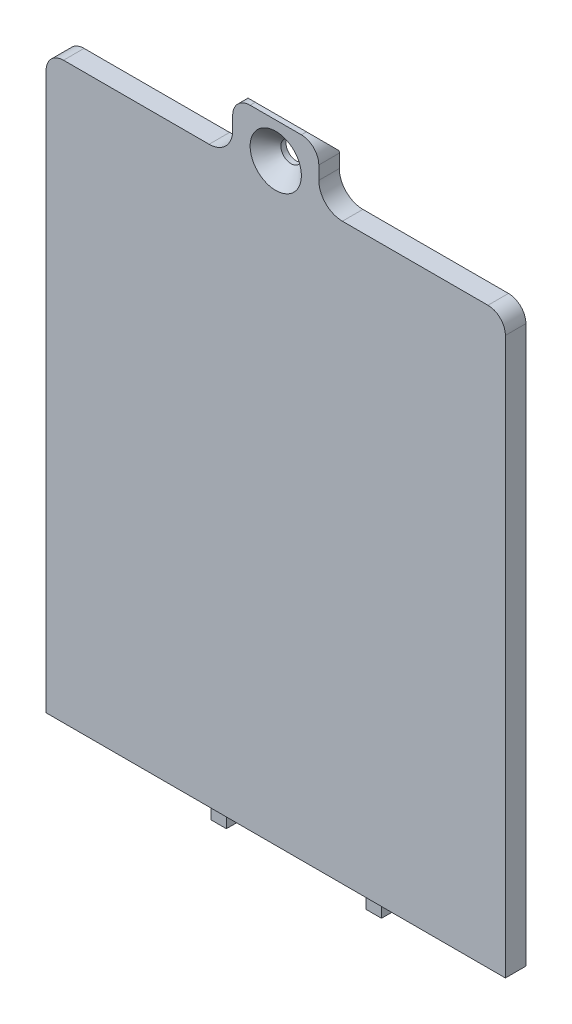
SolidWorks part; units mm, degrees
ref_plane "Front Plane" through (0, 0, 0) normal (0, 0, 1) x (1, 0, 0)
ref_plane "Top Plane" through (0, 0, 0) normal (0, 1, 0) x (1, 0, 0)
ref_plane "Right Plane" through (0, 0, 0) normal (1, 0, 0) x (0, 0, -1)
sketch "Sketch1" plane through (0, 0, 0) normal (0, 0, 1) x (1, 0, 0)
  line L28 (-23.2, -26.99) -> (-23.2, 27.29)
  line L29 (-21.5, 28.99) -> (-7.3, 28.99)
  line L30 (21.6, -26.99) -> (-23.2, -26.99)
  line L31 (21.6, 27.29) -> (21.6, -26.99)
  line L32 (5.7, 28.99) -> (19.9, 28.99)
  line L33 (-5, 31.29) -> (-5, 32.59)
  line L34 (-3.3, 34.29) -> (1.7, 34.29)
  line L35 (3.4, 32.59) -> (3.4, 31.29)
  arc A18 (-21.5, 28.99) -> (-23.2, 27.29) centre (-21.5, 27.29) ccw
  arc A19 (21.6, 27.29) -> (19.9, 28.99) centre (19.9, 27.29) ccw
  arc A20 (-7.3, 28.99) -> (-5, 31.29) centre (-7.3, 31.29) ccw
  arc A21 (-3.3, 34.29) -> (-5, 32.59) centre (-3.3, 32.59) ccw
  arc A22 (3.4, 32.59) -> (1.7, 34.29) centre (1.7, 32.59) ccw
  arc A23 (3.4, 31.29) -> (5.7, 28.99) centre (5.7, 31.29) ccw
extrude "Boss-Extrude1" add sketch "Sketch1" along normal blind 2
sketch "Sketch2" plane through (0, 0, 0) normal (0, 0, -1) x (-1, 0, 0)
  circle A0 centre (0.8, 30.84) radius 1
  dimension "D1" = 2
extrude "Cut-Extrude1" cut sketch "Sketch2" against normal up to next
sketch "Sketch3" plane through (0, 0, 0) normal (0, 0, -1) x (-1, 0, 0)
  line L0 (23.2, 27.29) -> (23.2, -26.99) construction
  line L1 (23.2, -26.99) -> (-21.6, -26.99) construction
  line L2 (22.2, 27.29) -> (-20.6, 27.29)
  line L3 (22.2, 27.29) -> (22.2, -25.99)
  line L4 (22.2, -25.99) -> (-20.6, -25.99)
  line L5 (-20.6, 27.29) -> (-20.6, -25.99)
  line L6 (-21.6, -26.99) -> (-21.6, 27.29) construction
  line L8 (23.5, 27.29) -> (-21.9, 27.29) construction
  point P14 (23.2, -25.3171)
  dimension "D1" = 1
  dimension "D2" = 1
  dimension "D3" = 1
extrude "Cut-Extrude2" cut sketch "Sketch3" against normal blind 1
sketch "Sketch4" plane through (0, 0, 1) normal (0, 0, -1) x (-1, 0, 0)
  line L0 (0.8, 27.29) -> (0.8, -25.99) construction
  line L1 (22.2, 27.29) -> (-20.6, 27.29) construction
  line L2 (-20.6, -25.99) -> (22.2, -25.99) construction
  line L3 (8.3665, 27.29) -> (8.3665, -25.99) construction
  line L4 (-6.7665, 27.29) -> (-6.7665, -25.99) construction
  line L5 (23.2, -26.99) -> (-21.6, -26.99) construction
  line L6 (-7.5165, 27.29) -> (-6.0165, 27.29)
  line L7 (-7.5165, 27.29) -> (-7.5165, -29.99)
  line L8 (-7.5165, -29.99) -> (-6.0165, -29.99)
  line L9 (-6.0165, 27.29) -> (-6.0165, -29.99)
  line L10 (9.1165, 27.29) -> (7.6165, 27.29)
  line L11 (9.1165, 27.29) -> (9.1165, -29.99)
  line L12 (9.1165, -29.99) -> (7.6165, -29.99)
  line L13 (7.6165, 27.29) -> (7.6165, -29.99)
  dimension "D1" = 15.133
  dimension "D2" = 1.5
  dimension "D3" = 3
extrude "Boss-Extrude2" add sketch "Sketch4" along normal blind 3.5
sketch "Sketch5" plane through (7.5165, 0, 0) normal (1, 0, 0) x (0, 0, -1)
  line L1 (0, -26.99) -> (-1, -26.99)
  line L2 (0, -26.99) -> (0, -29.99)
  line L3 (0, -29.99) -> (-1, -29.99)
  line L4 (-1, -26.99) -> (-1, -29.99)
extrude "Cut-Extrude3" cut sketch "Sketch5" against normal up to surface (16.633 mm away) up to face at (-9.1165, -9.3411, -0.1111)
chamfer "Chamfer1" distance 1 angle 45 2 edges at (-8.3665, -29.99, -2.5) (6.7665, -29.99, -2.5)
chamfer "Chamfer2" distance 2.5 angle 45 2 edges at (6.7665, 27.29, -2.5) (-8.3665, 27.29, -2.5)
chamfer "Chamfer3" distance 1.5 angle 45 1 edges at (-0.8, 34.29, 0) tangent propagation no
chamfer "Chamfer4" distance 1.5 angle 45 1 edges at (0.2, 30.84, 2)
